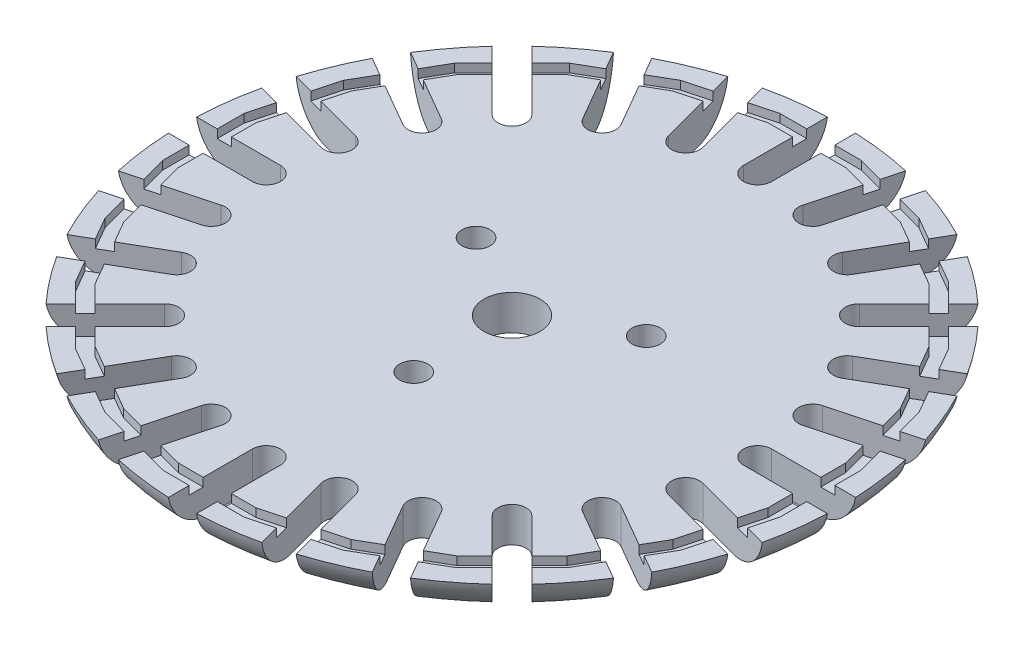
SolidWorks part; units mm, degrees
ref_plane "Plano frontal" through (0, 0, 0) normal (0, 0, 1) x (1, 0, 0)
ref_plane "Plano superior" through (0, 0, 0) normal (0, 1, 0) x (1, 0, 0)
ref_plane "Plano direito" through (0, 0, 0) normal (1, 0, 0) x (0, 0, -1)
sketch "Esboço1" plane through (0, 0, 0) normal (0, 1, 0) x (1, 0, 0)
  circle A0 centre (0, 0) radius 23.5
  dimension "D1" = 47
extrude "Ressalto-extrusão1" add sketch "Esboço1" along normal blind 2.5
fillet "Filete1" radius 3 1 edges at (0, 0, 23.5)
sketch "Esboço2" plane through (0, 2.5, 0) normal (0, 1, 0) x (1, 0, 0)
  line L0 (0, 0) -> (0, 23.9078) construction
  line L2 (1, 17.5) -> (1, 23.5)
  line L3 (1, 23.5) -> (-1, 23.5)
  line L4 (0, 23.5) -> (7.8408, 23.5) construction
  line L5 (-1, 17.5) -> (-1, 23.5)
  arc A0 (-1, 17.5) -> (1, 17.5) centre (0, 17.5) ccw
  circle A3 centre (0, 0) radius 23.5 construction
  point P12 (0, 16.5)
  dimension "D2" = 6
  dimension "D1" = 1
extrude "Corte-extrusão1" cut sketch "Esboço2" against normal through all
pattern_circular "PadrãoCircular1" count 24 over 360 about axis through (0, 2.5, 0) along (0, 1, 0) of "Corte-extrusão1"
sketch "Esboço4" plane through (0, 2.5, 0) normal (0, 1, 0) x (1, 0, 0)
  line L0 (0, 0) -> (-3.0674, 23.299) construction
  line L1 (0, 0) -> (3.0674, 23.299) construction
  line L2 (-2.8964, 22) -> (2.8964, 22)
  line L3 (2.8964, 22) -> (2.7647, 21)
  line L4 (2.7647, 21) -> (-2.7647, 21)
  line L5 (-2.7647, 21) -> (-2.8964, 22)
  arc A2 (5.1108, 22.9375) -> (1, 23.4787) centre (0, 0) ccw construction
  arc A3 (-1, 23.4787) -> (-5.1108, 22.9375) centre (0, 0) ccw construction
  dimension "D1" = 1
  dimension "D2" = 21
extrude "Corte-extrusão2" cut sketch "Esboço4" against normal blind 0.6
pattern_circular "PadrãoCircular2" count 24 over 360 about axis through (0, 2.5, 0) along (0, 1, 0) of "Corte-extrusão2"
sketch "Esboço5" plane through (0, 2.5, 0) normal (0, 1, 0) x (1, 0, 0)
  circle A0 centre (0, 0) radius 2
  dimension "D1" = 4
extrude "Corte-extrusão3" cut sketch "Esboço5" against normal through all
sketch "Esboço6" plane through (0, 0, 0) normal (0, -1, 0) x (1, 0, 0)
  circle A0 centre (0, 7) radius 1
  dimension "D1" = 2
  dimension "D2" = 7
extrude "Corte-extrusão4" cut sketch "Esboço6" against normal through all
sketch "Esboço7" plane through (0, 0, 0) normal (0, -1, 0) x (1, 0, 0)
  circle A0 centre (0, 7) radius 2
  dimension "D1" = 4
extrude "Corte-extrusão5" cut sketch "Esboço7" against normal blind 1
pattern_circular "PadrãoCircular3" count 3 over 360 about axis through (0, 0, 0) along (0, 1, 0) of "Corte-extrusão4", "Corte-extrusão5"
